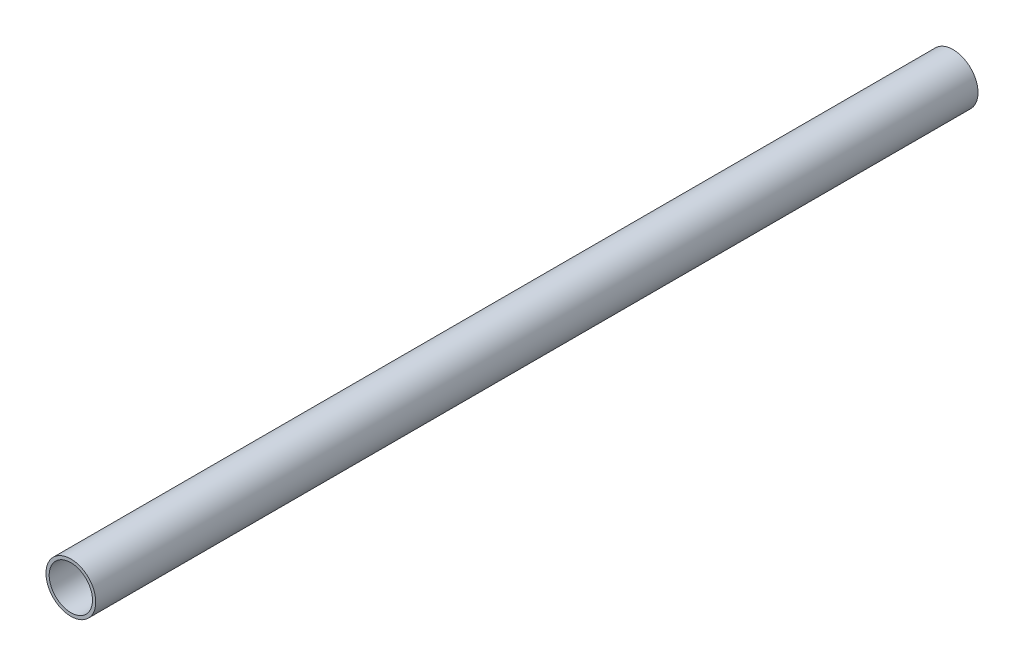
SolidWorks part; units mm, degrees
material "6063-T6, Rod (SS)"
ref_plane "Front Plane" through (0, 0, 0) normal (0, 0, 1) x (1, 0, 0)
ref_plane "Top Plane" through (0, 0, 0) normal (0, 1, 0) x (1, 0, 0)
ref_plane "Right Plane" through (0, 0, 0) normal (1, 0, 0) x (0, 0, -1)
sketch "Sketch1" plane through (0, 0, 0) normal (0, 0, 1) x (1, 0, 0)
  circle A0 centre (0, 0) radius 12.7
  circle A1 centre (0, 0) radius 11.049
  dimension "D1" = 25.4
  dimension "D2" = 22.098
extrude "Boss-Extrude1" add sketch "Sketch1" along normal blind 450
